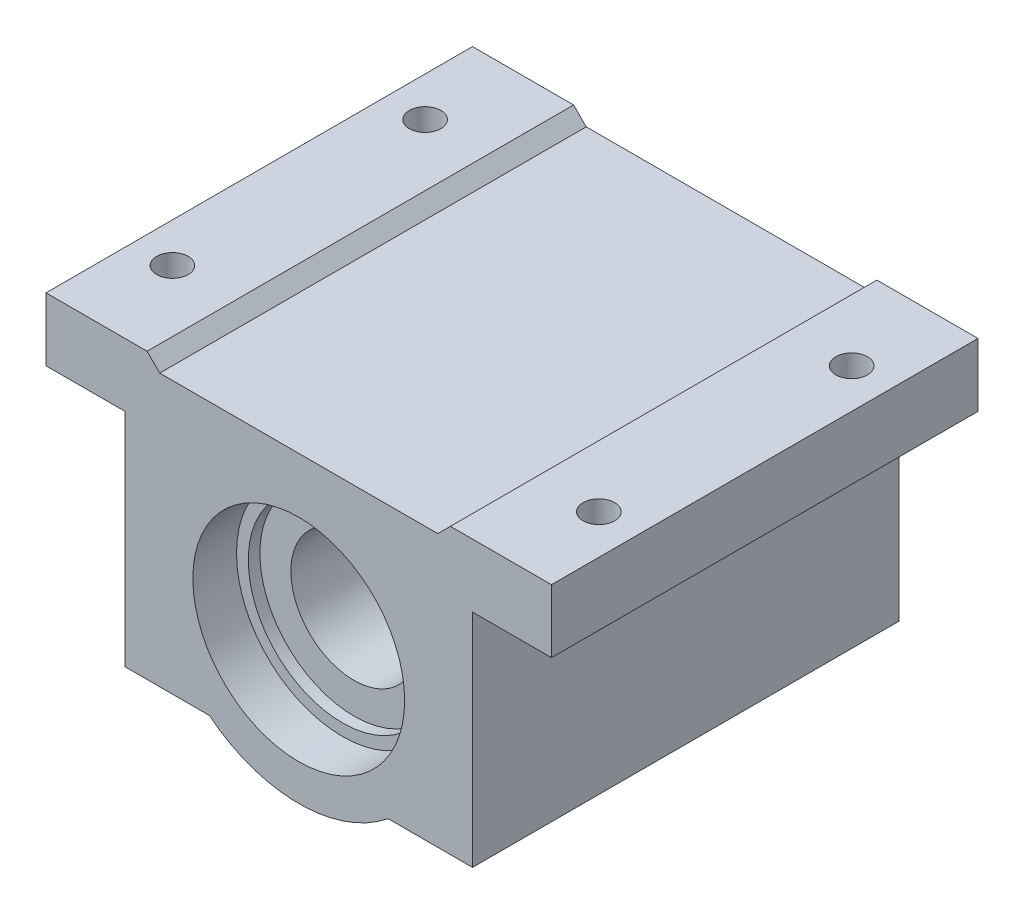
SolidWorks part; units mm, degrees
note: The reader was unsure of these and kept them because the rebuilt part matched: shared geometry of "Grooves<2>".
other "Pillow Block" parameters "D1"=31.4478, "For Shaft Dia"=12.7, "D2"=12.6007, "Supplier Grv Dia P"=23.6474, "Ht G"=17.4625, "Flange Thick H"=6.35, "Overall Wd D"=50.8, "Overall Ht F"=31.75, "Supplier Wd G"=25.4, "D3"=16.7204, "D4"=1.4178, "D5"=41.275, "D6"=12.2773, "D7"=50.8, "Supplier Body Height K"=28.575, "Overall Lg B"=42.8625, "Supplier Overall Wd S"=119.0625, "Outside to Outside Grooves"=228.6, "Supplier Grv Wd O"=1.1684, "Dia L"=3.175, "Mounting Holes Center-to-Center J"=42.8625, "Mounting Holes Center-to-Center K"=25.4, "Supplier F"=25.4
ref_plane "Front" through (0, 0, 0) normal (0, 0, 1) x (1, 0, 0)
ref_plane "Top" through (0, 0, 0) normal (0, 1, 0) x (1, 0, 0)
ref_plane "Right" through (0, 0, 0) normal (1, 0, 0) x (0, 0, -1)
sketch "Sketch1" plane through (0, 0, 0) normal (0, 0, 1) x (1, 0, 0)
  line L0 (-17.4625, -14.2875) -> (-17.4625, 11.1125) construction
  line L1 (-17.4625, -14.2875) -> (17.4625, -14.2875) construction
  line L2 (-17.4625, 11.1125) -> (-25.4, 11.1125)
  line L3 (-25.4, 17.4625) -> (25.4, 17.4625) construction
  line L4 (-25.4, 11.1125) -> (-25.4, 17.4625)
  line L5 (17.4625, -14.2875) -> (17.4625, 11.1125) construction
  line L6 (17.4625, 11.1125) -> (25.4, 11.1125)
  line L7 (25.4, 11.1125) -> (25.4, 17.4625)
  line L8 (0, 17.4625) -> (0, -14.2875) construction
  line L9 (8.9803, -11.1125) -> (17.4625, -11.1125)
  line L10 (-17.4625, 11.1125) -> (-17.4625, -11.1125)
  line L11 (-17.4625, -11.1125) -> (-8.9803, -11.1125)
  line L12 (17.4625, -11.1125) -> (17.4625, 11.1125)
  line L13 (-15.24, 17.4625) -> (15.24, 17.4625) construction
  line L14 (-15.24, 17.4625) -> (-13.97, 16.1925)
  line L15 (-13.97, 16.1925) -> (13.97, 16.1925)
  line L16 (13.97, 16.1925) -> (15.24, 17.4625)
  line L17 (-15.24, 17.4625) -> (-25.4, 17.4625)
  line L18 (15.24, 17.4625) -> (25.4, 17.4625)
  circle A0 centre (0, 0) radius 6.35 construction
  circle A1 centre (0, 0) radius 10.6413
  circle A2 centre (0, 0) radius 14.2875 construction
  arc A3 (-8.9803, -11.1125) -> (8.9803, -11.1125) centre (0, 0) ccw
  circle A4 centre (0, 0) radius 11.8237 construction
  dimension "D2" = 21.2827
  dimension "D4" = 45
  dimension "D3" = 45
  dimension "D6" = 10.16
  dimension "D1" = 1.27
extrude "Main Body" add sketch "Sketch1" along normal mid plane 42.8625
sketch "Sketch3" plane through (0, 17.4625, 0) normal (0, 1, 0) x (1, 0, 0)
  line L1 (-21.4313, -12.7) -> (21.4312, -12.7) construction
  line L2 (-21.4313, -12.7) -> (-21.4313, 12.7) construction
  line L3 (-21.4313, 12.7) -> (21.4312, 12.7) construction
  line L4 (21.4312, -12.7) -> (21.4312, 12.7) construction
  line L5 (-15.24, 21.4312) -> (-25.4, 21.4312) construction
  line L6 (-21.4313, 12.7) -> (21.4312, -12.7) construction
  line L7 (-21.4313, 12.7) -> (-21.4313, -12.7) construction
  circle A0 centre (-21.4313, 12.7) radius 1.5875
  circle A1 centre (21.4312, 12.7) radius 1.5875
  circle A2 centre (21.4312, -12.7) radius 1.5875
  circle A3 centre (-21.4313, -12.7) radius 1.5875
  point P5 (0, 0)
  dimension "D1" = 8.7312
extrude "Mounting Holes" cut sketch "Sketch3" against normal up to surface (6.35 mm away) up to face at (21.4313, 11.1125, 0)
ref_plane "Plane1" through (0, 0, 0) normal (0, 0, 1) x (1, 0, 0)
sketch "Sketch8" plane through (0, 0, 0) normal (0, 0, 1) x (1, 0, 0)
  circle A0 centre (0, 0) radius 10.6413 construction
  circle A1 centre (0, 0) radius 10.6413
  circle A2 centre (0, 0) radius 6.35 construction
  circle A3 centre (0, 0) radius 6.35
extrude "Interior" add sketch "Sketch8" along normal mid plane 31.75 separate body
sketch "Grooves" plane through (0, 0, 0) normal (1, 0, 0) x (0, 0, -1)
  line L1 (15.875, -11.8237) -> (15.875, 11.8237) construction
  line L2 (15.875, -6.35) -> (15.875, 6.35) construction
  line L4 (-15.875, 6.35) -> (-15.875, -6.35) construction
  line L5 (15.875, -9.459) -> (15.875, -11.8237)
  line L6 (15.875, -11.8237) -> (17.0434, -11.8237)
  line L7 (17.0434, -9.459) -> (17.0434, -11.8237)
  line L9 (-15.875, -9.459) -> (-15.875, -11.8237)
  line L10 (-15.875, -11.8237) -> (-17.0434, -11.8237)
  line L11 (-17.0434, -9.459) -> (-17.0434, -11.8237)
  line L13 (-17.0434, -9.459) -> (-15.875, -9.459)
  line L14 (15.875, -9.459) -> (17.0434, -9.459)
  line L15 (15.875, -9.459) -> (15.875, 9.459) construction
  point P13 (15.875, 0)
  dimension "Supplier Grv Dia P" = 23.6474
  dimension "D1" = 18.9179
revolve "Grooves " cut sketch "Grooves" angle 360 mid plane about axis through (0, 0, 15.875) along (0, 0, -1)
revolve "Retaining Ring" add sketch "Grooves<2>" angle 360 mid plane about axis through (0, 0, 15.875) along (0, 0, -1)
sketch "Grooves<2>" plane through (0, 0, 0) normal (1, 0, 0) x (0, 0, -1) same geometry as "Grooves"
sketch "Open Retaining Ring" [suppressed] plane through (0, 0, 0) normal (0, 0, 1) x (1, 0, 0)
  line L0 (0, 0) -> (-42.7798, -49.2125)
  line L1 (-42.7798, -49.2125) -> (42.7798, -49.2125)
  line L2 (42.7798, -49.2125) -> (0, 0)
  arc A0 (-31.149, -38.1) -> (31.149, -38.1) centre (0, 0) ccw construction
  dimension "D1" = 82
extrude "Open Retaining Ring " [suppressed] cut sketch "Open Retaining Ring" against normal mid plane 42.8625
sketch "Jog" [suppressed] plane through (0, 0, 0) normal (0, 0, 1) x (1, 0, 0)
  line L0 (57.15, -38.1) -> (-61.9125, -38.1) construction
  line L1 (-57.15, -38.1) -> (-61.9125, -38.1)
  line L2 (-61.9125, -38.1) -> (-61.9125, -19.685)
  line L3 (-61.9125, -19.685) -> (-57.15, -14.9225)
  line L4 (-57.15, 38.1) -> (-57.15, -38.1) construction
  line L5 (-57.15, -14.9225) -> (-57.15, -38.1)
  dimension "D1" = 45
  dimension "D2" = 5.715
extrude "Jog " [suppressed] add sketch "Jog" along normal mid plane 42.8625
sketch "Slot Opening" [suppressed] plane through (0, 0, 0) normal (0, 0, 1) x (1, 0, 0)
  line L0 (0, 0) -> (0, -21.997) construction
  line L1 (-12.7, -21.997) -> (12.7, -21.997)
  line L2 (-12.7, -21.997) -> (-21.997, -38.1)
  line L3 (12.7, -21.997) -> (21.997, -38.1)
  line L4 (21.997, -38.1) -> (31.149, -38.1)
  line L5 (-31.149, -38.1) -> (-21.997, -38.1)
  line L6 (31.149, -38.1) -> (31.149, -49.2125)
  line L7 (31.149, -49.2125) -> (-31.149, -49.2125)
  line L8 (-31.149, -49.2125) -> (-31.149, -38.1)
  line L9 (-57.15, -49.2125) -> (57.15, -49.2125) construction
  circle A0 centre (0, 0) radius 25.4 construction
  dimension "D1" = 60
  dimension "Wd E" = 25.4
extrude "Slot Opening " [suppressed] cut sketch "Slot Opening" against normal through all and the other way through all
mirror "Twin Holes Mirror" [suppressed] about plane through (0, 0, 0) normal (0, 0, 1)
mirror "Twin Bodies" [suppressed] about plane through (0, 0, 0) normal (0, 0, 1)
mirror "Twin Grooves" [suppressed] about plane through (0, 0, 0) normal (0, 0, 1)
equation "\"D6@Sketch1\" = \"Overall Wd D@Sketch1\"  * .2"
equation "\"D1@Sketch1\" = \"Flange Thick H@Sketch1\" * .2"
equation "\"D1@Jog \" = \"Overall Lg B@Main Body\""
equation "\"D2@Jog\" = \"Supplier Body Height K@Sketch1\" * .2"
equation "\"Supplier Grv Dia P@Grooves\" = \"Supplier Grv Dia P@Sketch1\""
equation "\"D2@Sketch1\" = \"Supplier Grv Dia P@Sketch1\" * .9"
equation "\"D1@Grooves\" = \"Supplier Grv Dia P@Sketch1\" * .8"
equation "\"D1@Sketch3\" =  ( \"Overall Lg B@Main Body\" - \"Supplier F@Sketch3\" )  * .5"
equation "\"D1@Open Retaining Ring \" = \"Overall Lg B@Main Body\""
